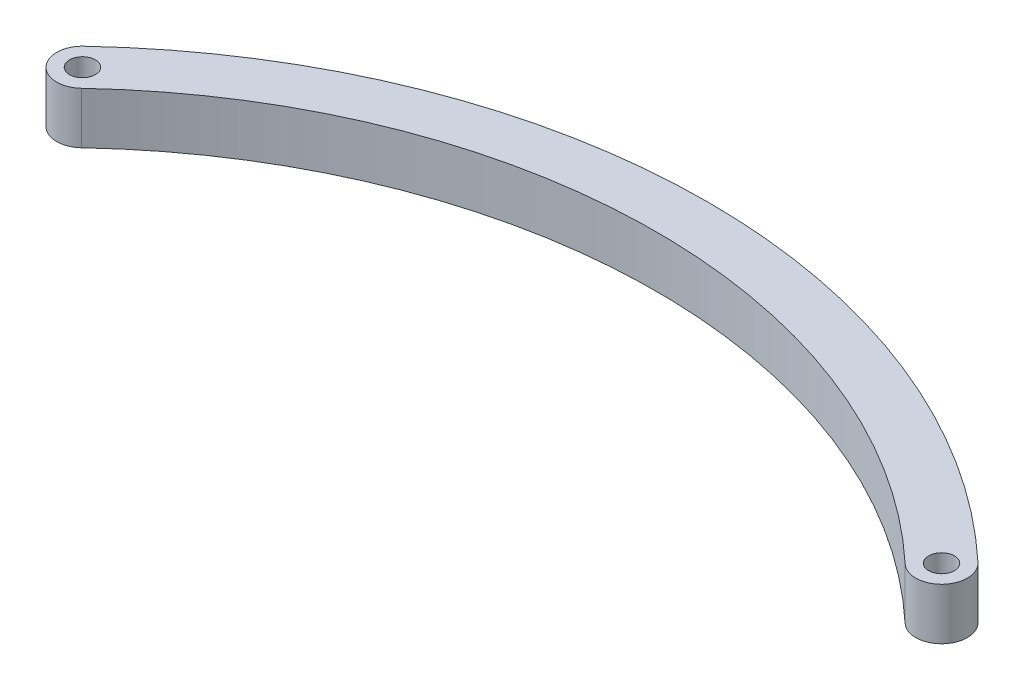
SolidWorks part; units mm, degrees
ref_plane "Front Plane" through (0, 0, 0) normal (0, 0, 1) x (1, 0, 0)
ref_plane "Top Plane" through (0, 0, 0) normal (0, 1, 0) x (1, 0, 0)
ref_plane "Right Plane" through (0, 0, 0) normal (1, 0, 0) x (0, 0, -1)
sketch "Esquisse1" plane through (0, 0, 0) normal (0, 1, 0) x (1, 0, 0)
  line L0 (-50, 0) -> (0, 0) construction
  line L1 (0, 0) -> (50, 0) construction
  circle A0 centre (-50, 0) radius 1.5
  circle A1 centre (50, 0) radius 1.5
  circle A2 centre (-50, 0) radius 3
  circle A3 centre (50, 0) radius 3
  circle A4 centre (0, -53.1883) radius 70
  circle A5 centre (0, -53.1883) radius 76
  dimension "D2" = 3
  dimension "D3" = 6
  dimension "D4" = 140
  dimension "D5" = 152
  dimension "D1" = 50
extrude "Boss.-Extru.1" add sketch "Esquisse1" along normal blind 6 contours A3 A5 A2 A4 | A2 A0 | A3 A1 region at (-47.3243, 0, 1.157) region at (-48.3843, 0, -3.7363) region at (52.6757, 0, -1.157)
